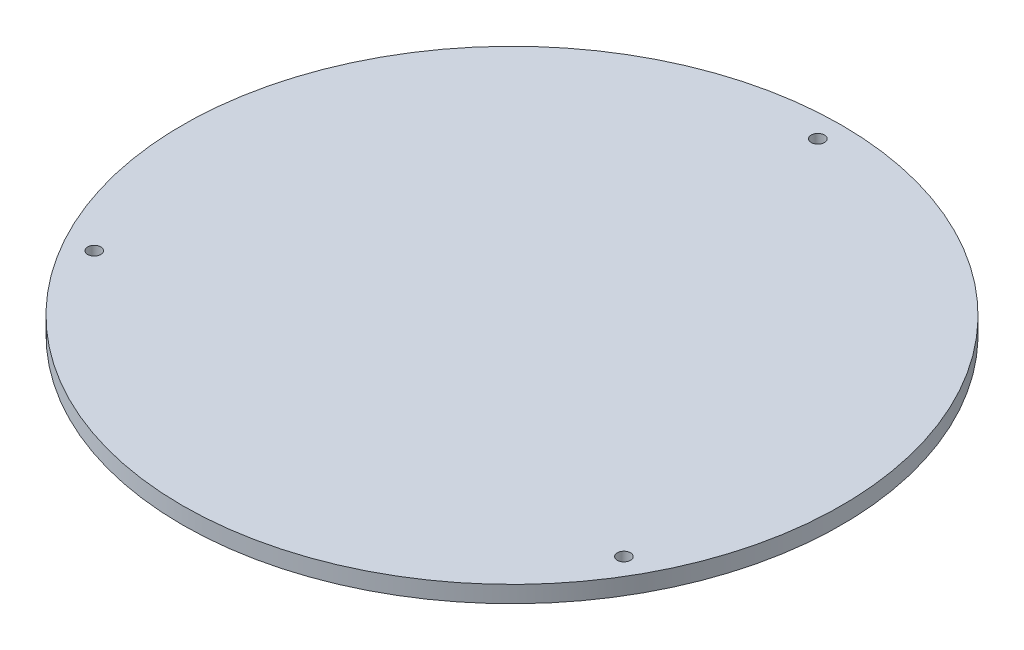
SolidWorks part; units mm, degrees
ref_plane "Front Plane" through (0, 0, 0) normal (0, 0, 1) x (1, 0, 0)
ref_plane "Top Plane" through (0, 0, 0) normal (0, 1, 0) x (1, 0, 0)
ref_plane "Right Plane" through (0, 0, 0) normal (1, 0, 0) x (0, 0, -1)
sketch "Sketch1" plane through (0, 0, 0) normal (0, 1, 0) x (1, 0, 0)
  circle A0 centre (0, 0) radius 125
  circle A1 centre (0, 116) radius 2.5
  dimension "D1" = 250
  dimension "D2" = 5
  dimension "D3" = 9
extrude "Boss-Extrude1" add sketch "Sketch1" along normal blind 6.35 contours A0
sketch "Sketch2" plane through (0, 6.35, 0) normal (0, 1, 0) x (1, 0, 0)
  line L0 (0, 0) -> (0, 125) construction
  line L1 (0, 0) -> (108.2532, -62.5) construction
  line L2 (0, 0) -> (-108.2532, -62.5) construction
  line L3 (0, 0) -> (0, 125) construction
  line L4 (0, 0) -> (108.2532, -62.5) construction
  circle A0 centre (0, 0) radius 125 construction
  circle A1 centre (0, 116) radius 2.5
  circle A2 centre (100.4589, -58) radius 2.5
  circle A3 centre (-100.4589, -58) radius 2.5
  dimension "D3" = 5
  dimension "D2" = 120
  dimension "D4" = 9
  dimension "D1" = 3
ref_plane "Plane1" through (0, 13.35, 0) normal (0, 1, 0) x (1, 0, 0)
sketch "Sketch3" plane through (0, 13.35, 0) normal (0, 1, 0) x (1, 0, 0)
  circle A0 centre (100.4589, -58) radius 2.5 construction
  circle A1 centre (0, 116) radius 2.5 construction
  circle A2 centre (-100.4589, -58) radius 2.5 construction
  point P0 (0, 116)
  point P1 (100.4589, -58)
  point P3 (-100.4589, -58)
extrude "Cut-Extrude1" cut sketch "Sketch2" against normal through all
sketch "Sketch4" plane through (0, 0, 0) normal (0, -1, 0) x (1, 0, 0)
  line L4 (0, -5) -> (0, 5)
  line L12 (-15, 0) -> (15, 0) construction
  line L13 (-35, 10) -> (-15, 10) construction
  line L14 (-15, 20) -> (-20, 20) construction
  line L15 (-25, 0) -> (-20, 0)
  line L16 (-20, 20) -> (-25, 20)
  line L17 (-15, 20) -> (-15, -20)
  line L18 (35, -20) -> (15, -20) construction
  line L19 (5, 0) -> (-5, 0)
  line L20 (15, 20) -> (15, -20)
  line L21 (25, 5) -> (15, 20)
  line L22 (35, 20) -> (25, 5)
  line L23 (35, -20) -> (35, 20)
  arc A1 (-25, 20) -> (-25, 0) centre (-25, 10) ccw
  point P21 (0, 0)
  dimension "D1" = 10
  dimension "D3" = 30
extrude "Cut-Extrude-Thin1" [suppressed] cut sketch "Sketch4" against normal blind 1 thin thin type mid plane wall 1
sketch "Sketch6" plane through (0, 6.35, 0) normal (0, 1, 0) x (1, 0, 0)
  line L0 (0, 116) -> (0, 0) construction
  line L1 (10, 116) -> (10, 0)
  line L2 (-10, 116) -> (-10, 0)
  line L3 (0, 0) -> (100.4589, -58) construction
  line L4 (5, 8.6603) -> (105.4589, -49.3397)
  line L5 (-5, -8.6603) -> (95.4589, -66.6603)
  line L6 (0, 0) -> (-100.4589, -58) construction
  line L7 (5, -8.6603) -> (-95.4589, -66.6603)
  line L8 (-5, 8.6603) -> (-105.4589, -49.3397)
  arc A0 (10, 116) -> (-10, 116) centre (0, 116) ccw
  arc A1 (-10, 0) -> (10, 0) centre (0, 0) ccw
  arc A2 (5, 8.6603) -> (-5, -8.6603) centre (0, 0) ccw
  arc A3 (95.4589, -66.6603) -> (105.4589, -49.3397) centre (100.4589, -58) ccw
  arc A4 (5, -8.6603) -> (-5, 8.6603) centre (0, 0) ccw
  arc A5 (-105.4589, -49.3397) -> (-95.4589, -66.6603) centre (-100.4589, -58) ccw
  circle A6 centre (0, 0) radius 125 construction
  circle A7 centre (100.4589, -58) radius 2.5 construction
  circle A8 centre (-100.4589, -58) radius 2.5 construction
  circle A9 centre (0, 116) radius 2.5 construction
  circle A10 centre (0, 0) radius 125
  circle A11 centre (100.4589, -58) radius 2.5
  circle A12 centre (-100.4589, -58) radius 2.5
  circle A13 centre (0, 116) radius 2.5
  point P4 (0, 58)
  point P9 (50.2295, -29)
  point P17 (-50.2295, -29)
  circle M16 centre (0, 0) radius 125
  dimension "D1" = 10
extrude "Cut-Extrude2" [suppressed] cut sketch "Sketch6" against normal blind 10 contours A5 L8 L2 A0 M16 | A3 A0 L1 L4 M16 | A5 A3 L5 L7 M16
